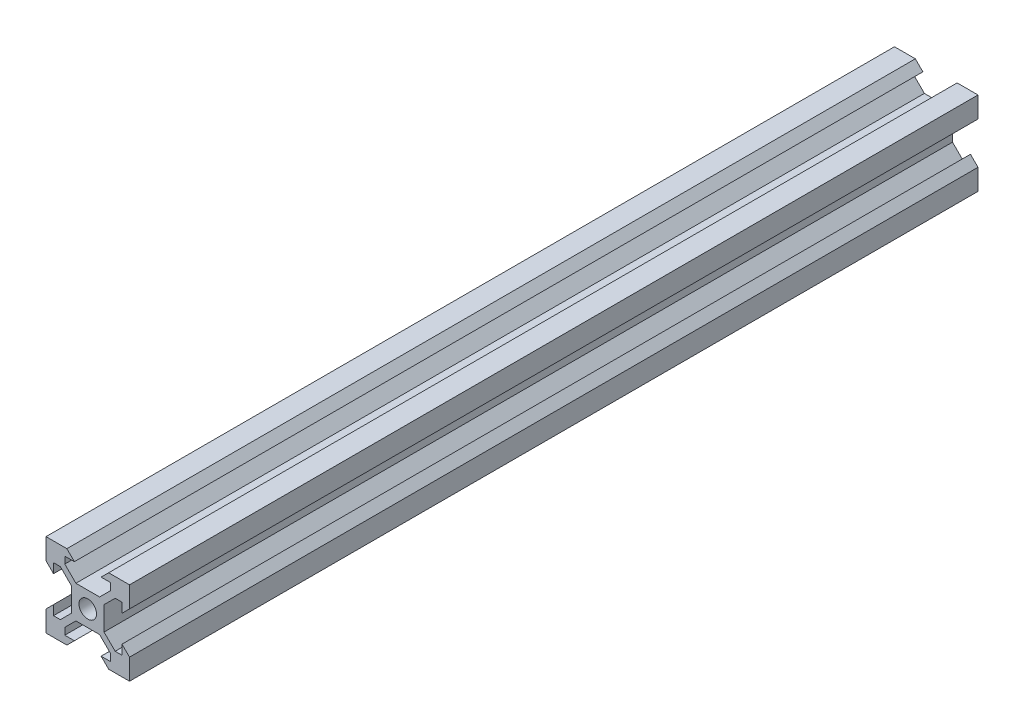
SolidWorks part; units mm, degrees
material "6063-T5"
ref_plane "Front Plane" through (0, 0, 0) normal (0, 0, 1) x (1, 0, 0)
ref_plane "Top Plane" through (0, 0, 0) normal (0, 1, 0) x (1, 0, 0)
ref_plane "Right Plane" through (0, 0, 0) normal (1, 0, 0) x (0, 0, -1)
sketch "Sketch1" plane through (0, 0, 0) normal (0, 0, 1) x (1, 0, 0)
  line L0 (-10, 10) -> (-5, 10)
  line L1 (10, -10) -> (-10, -10) construction
  line L2 (10, -10) -> (10, 10) construction
  line L3 (10, 10) -> (-10, 10) construction
  line L4 (-10, -10) -> (-10, 10) construction
  line L5 (10, -10) -> (-10, 10) construction
  line L6 (10, 10) -> (-10, -10) construction
  line L7 (-5, 10) -> (-3.2, 8.2)
  line L8 (-3.2, 8.2) -> (-5.4993, 8.2)
  line L9 (-5.4993, 8.2) -> (-5.4993, 6.56)
  line L10 (-2.84, 3.9007) -> (2.84, 3.9007)
  line L11 (0, 3.9007) -> (0, 2.1) construction
  line L12 (-5.4993, 6.56) -> (-2.84, 3.9007)
  line L13 (0, 0) -> (0, -13.2939) construction
  line L14 (0, 0) -> (-17.0802, 0) construction
  line L15 (-10, 10) -> (-10, 5)
  line L16 (-10, 5) -> (-8.2, 3.2)
  line L17 (-8.2, 3.2) -> (-8.2, 5.4993)
  line L18 (-8.2, 5.4993) -> (-6.56, 5.4993)
  line L19 (-6.56, 5.4993) -> (-3.9007, 2.84)
  line L20 (-3.9007, 2.84) -> (-3.9007, -2.84)
  line L21 (-3.2, -8.2) -> (-5.4993, -8.2)
  line L22 (-5.4993, -8.2) -> (-5.4993, -6.56)
  line L23 (-5, -10) -> (-3.2, -8.2)
  line L24 (-10, -10) -> (-5, -10)
  line L25 (-10, -10) -> (-10, -5)
  line L26 (-10, -5) -> (-8.2, -3.2)
  line L27 (-8.2, -3.2) -> (-8.2, -5.4993)
  line L28 (-8.2, -5.4993) -> (-6.56, -5.4993)
  line L29 (-6.56, -5.4993) -> (-3.9007, -2.84)
  line L30 (-5.4993, -6.56) -> (-2.84, -3.9007)
  line L31 (-2.84, -3.9007) -> (2.84, -3.9007)
  line L32 (5.4993, 6.56) -> (2.84, 3.9007)
  line L33 (3.2, 8.2) -> (5.4993, 8.2)
  line L34 (5.4993, 8.2) -> (5.4993, 6.56)
  line L35 (5, 10) -> (3.2, 8.2)
  line L36 (10, 10) -> (5, 10)
  line L37 (10, 10) -> (10, 5)
  line L38 (10, 5) -> (8.2, 3.2)
  line L39 (8.2, 3.2) -> (8.2, 5.4993)
  line L40 (8.2, 5.4993) -> (6.56, 5.4993)
  line L41 (6.56, 5.4993) -> (3.9007, 2.84)
  line L42 (3.9007, 2.84) -> (3.9007, -2.84)
  line L43 (6.56, -5.4993) -> (3.9007, -2.84)
  line L44 (8.2, -5.4993) -> (6.56, -5.4993)
  line L45 (8.2, -3.2) -> (8.2, -5.4993)
  line L46 (10, -5) -> (8.2, -3.2)
  line L47 (10, -10) -> (10, -5)
  line L48 (10, -10) -> (5, -10)
  line L49 (5, -10) -> (3.2, -8.2)
  line L50 (3.2, -8.2) -> (5.4993, -8.2)
  line L51 (5.4993, -8.2) -> (5.4993, -6.56)
  line L52 (5.4993, -6.56) -> (2.84, -3.9007)
  circle A0 centre (0, 0) radius 2.1
  arc A1 (0, -2.1) -> (0, 2.1) centre (0, 0) cw construction
  point P0 (0, 0)
  point P25 (-3.9007, 0)
  point P35 (0, 0)
  point P56 (0, -3.9007)
  dimension "D2" = 4.2
  dimension "D1" = 20
  dimension "D3" = 1.64
  dimension "D4" = 1.8
  dimension "D5" = 45
  dimension "D6" = 1.5
  dimension "D7" = 5.68
  dimension "D8" = 5
extrude "Boss-Extrude1" add sketch "Sketch1" along normal mid plane 203.2
